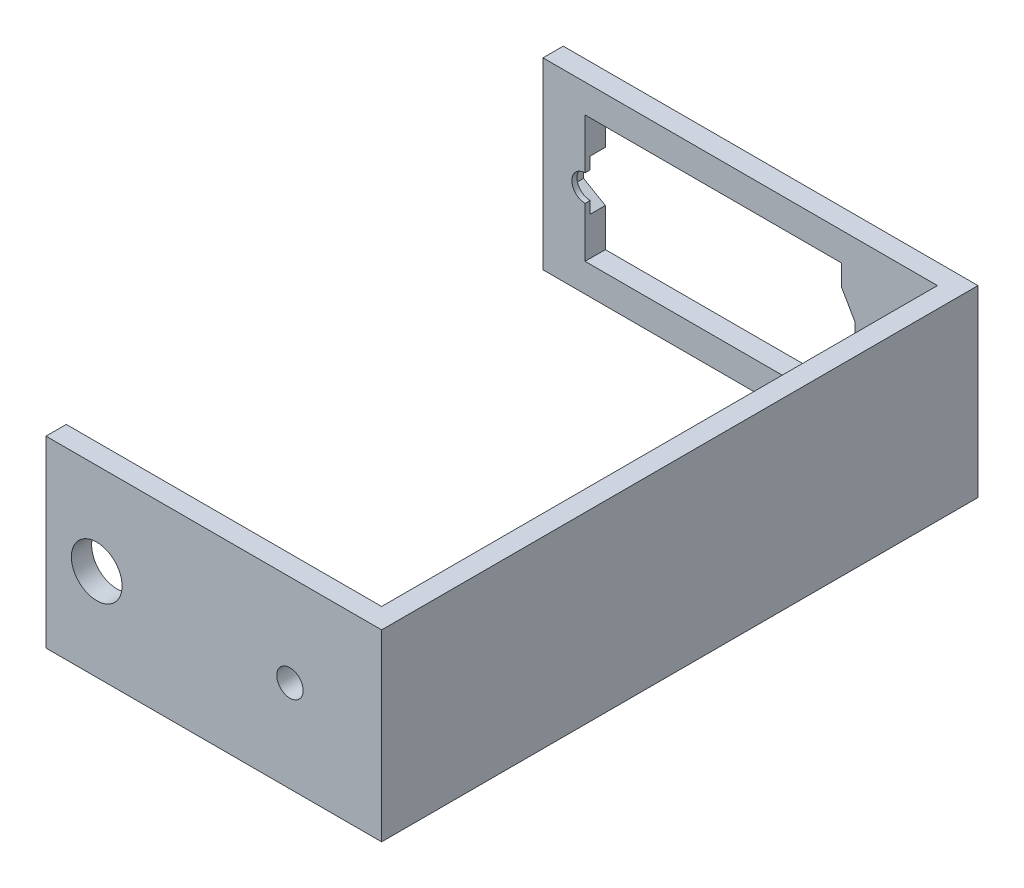
SolidWorks part; units mm, degrees
ref_plane "Front Plane" through (0, 0, 0) normal (0, 0, 1) x (1, 0, 0)
ref_plane "Top Plane" through (0, 0, 0) normal (0, 1, 0) x (1, 0, 0)
ref_plane "Right Plane" through (0, 0, 0) normal (1, 0, 0) x (0, 0, -1)
sketch "Sketch2" plane through (-4.7256, 0, 0) normal (1, 0, 0) x (0, 1, 0)
  line L0 (-22.4995, 27.5679) -> (-27.1995, 27.5679) construction
  line L1 (-33.8995, 25.5679) -> (-15.7995, 25.5679)
  line L2 (-33.8995, 25.5679) -> (-33.8995, -29.2321)
  line L3 (-33.8995, -29.2321) -> (-15.7995, -29.2321)
  line L4 (-15.7995, 25.5679) -> (-15.7995, -29.2321)
  line L5 (-22.4995, 27.5679) -> (-27.1995, 27.5679) construction
  line L6 (-24.8495, 27.5679) -> (-24.8495, 25.5679) construction
  line L7 (-30.8995, -25.9321) -> (-30.8995, -28.9321) construction
  dimension "D1" = 2
  dimension "D2" = 0.3
  dimension "D3" = 3
extrude "Boss-Extrude1" add sketch "Sketch2" along normal blind 2 from offset 26.09
sketch "Sketch3" plane through (0, 0, 25.5679) normal (0, 0, 1) x (1, 0, 0)
  line L0 (23.3644, -15.7995) -> (21.3644, -15.7995) construction
  line L1 (23.3644, -33.8995) -> (-9.7256, -33.8995)
  line L2 (23.3644, -33.8995) -> (23.3644, -15.7995)
  line L3 (23.3644, -15.7995) -> (-9.7256, -15.7995)
  line L4 (-9.7256, -33.8995) -> (-9.7256, -15.7995)
  line L5 (23.3644, -15.7995) -> (23.3644, -33.8995) construction
  circle A0 centre (-4.7256, -24.8495) radius 2.35 construction
  circle A1 centre (-4.7256, -24.8495) radius 2.35 construction
  circle A2 centre (-4.7256, -24.8495) radius 2.5
  dimension "D1" = 5
  dimension "D2" = 5
extrude "Boss-Extrude2" add sketch "Sketch3" along normal blind 2
sketch "Sketch4" plane through (0, 0, -29.2321) normal (0, 0, -1) x (-1, 0, 0)
  line L0 (-23.3644, -33.8995) -> (-21.3644, -33.8995) construction
  line L1 (-23.3644, -15.7995) -> (17.5256, -15.7995)
  line L2 (-23.3644, -15.7995) -> (-23.3644, -33.8995)
  line L3 (-23.3644, -33.8995) -> (17.5256, -33.8995)
  line L4 (17.5256, -15.7995) -> (17.5256, -33.8995)
  line L5 (13.3756, -22.3669) -> (13.3756, -15.7995)
  line L6 (11.2256, -23.6082) -> (11.2256, -26.0908)
  line L7 (11.2256, -26.0908) -> (13.3756, -27.3321)
  line L8 (13.3756, -27.3321) -> (15.5256, -26.0908)
  line L9 (15.5256, -26.0908) -> (15.5256, -23.6082)
  line L10 (15.5256, -23.6082) -> (13.3756, -22.3669)
  line L11 (13.3756, -22.3669) -> (11.2256, -23.6082)
  line L12 (13.3756, -27.3321) -> (13.3756, -33.8995)
  line L13 (-0.4744, -30.8995) -> (-0.4744, -18.7995) construction
  line L14 (-12.1744, -26.0908) -> (-14.3244, -27.3321)
  line L15 (-13.2494, -22.9875) -> (-13.2494, -26.7114)
  line L16 (13.3756, -22.3669) -> (13.3756, -27.3321)
  line L19 (-11.7244, -18.7995) -> (-11.7244, -30.8995)
  line L20 (-11.7244, -30.8995) -> (10.7756, -30.8995)
  line L21 (10.7756, -30.8995) -> (10.7756, -18.7995)
  line L22 (10.7756, -18.7995) -> (-11.7244, -18.7995)
  line L23 (-11.7244, -18.7995) -> (-11.7244, -30.8995) construction
  line L24 (-11.7244, -30.8995) -> (10.7756, -30.8995) construction
  line L25 (10.7756, -30.8995) -> (10.7756, -18.7995) construction
  line L26 (10.7756, -18.7995) -> (-11.7244, -18.7995) construction
  line L27 (-14.3244, -27.3321) -> (-16.4744, -26.0908)
  line L28 (-16.4744, -26.0908) -> (-16.4744, -23.6082)
  line L29 (-16.4744, -23.6082) -> (-14.3244, -22.3669)
  line L30 (-14.3244, -22.3669) -> (-12.1744, -23.6082)
  line L31 (-11.9244, -18.5995) -> (-11.9244, -31.0995)
  line L32 (-11.9244, -31.0995) -> (10.9756, -31.0995)
  line L33 (10.9756, -31.0995) -> (10.9756, -18.5995)
  line L34 (10.9756, -18.5995) -> (-11.9244, -18.5995)
  line L35 (-11.9244, -18.5995) -> (-11.9244, -20.6926)
  line L36 (-11.9244, -31.0995) -> (13.3756, -31.0995)
  line L38 (13.3756, -18.5995) -> (-11.9244, -18.5995)
  line L39 (-12.1744, -23.6082) -> (-12.1744, -26.0908)
  line L40 (-13.2494, -22.9875) -> (-11.9244, -20.6926)
  line L41 (-13.2494, -26.7114) -> (-11.9244, -29.0064)
  line L42 (-11.9244, -29.0064) -> (-11.9244, -31.0995)
  line L43 (-11.9244, -20.6926) -> (-11.9244, -29.0064) construction
  circle A0 centre (-14.3244, -24.8495) radius 1.1 construction
  circle A1 centre (13.3756, -24.8495) radius 1.1 construction
  circle A2 centre (-14.3244, -24.8495) radius 1.1 construction
  circle A3 centre (13.3756, -24.8495) radius 1.1 construction
  circle A4 centre (13.3756, -24.8495) radius 2.15 construction
  circle A5 centre (-14.3244, -24.8495) radius 2.15 construction
  line M26 (-21.3644, -33.8995) -> (-21.3644, -15.7995)
  line M27 (-21.3644, -15.7995) -> (-23.3644, -15.7995)
  line M28 (-23.3644, -15.7995) -> (-23.3644, -33.8995)
  line M29 (-23.3644, -33.8995) -> (-21.3644, -33.8995)
  dimension "D1" = 4.3
  dimension "D4" = 2
  dimension "D2" = 0
  dimension "D3" = 0.2
extrude "Boss-Extrude3" add sketch "Sketch4" along normal blind 2 contours M29 M26 M27 M28 | L38 L5 L1 L3 L12 L36 L35 L30 L39 L14 L27 L28 L29 M26 | L8 L12 L3 L4 L1 L5 L10 L9 | L30 L29 L28 L27 L14 L15 | L10 L16 L8 L9 region at (22.3644, -24.8495, -29.2321) region at (3.9944, -16.1912, -29.2321) region at (-15.5842, -24.8495, -29.2321) region at (-14.3312, -24.8495, -29.2321) region at (14.7393, -24.8495, -29.2321)
extrude "Cut-Extrude5" cut sketch "Sketch4<3>" against normal blind 1.5 from surface contours L30 L29 L28 L27 L14 L15 | L10 L16 L8 L9 region at (-14.3312, -24.8495, -29.2321) region at (14.7393, -24.8495, -29.2321) starting at face at (5.9306, -24.8495, -31.2321)
sketch "Sketch4<3>" plane through (0, 0, -29.2321) normal (0, 0, -1) x (-1, 0, 0) same geometry as "Sketch4"
sketch "Sketch5" plane through (0, 0, -31.2321) normal (0, 0, -1) x (-1, 0, 0)
  line L0 (13.3756, -27.3321) -> (13.3756, -22.3669) construction
  point P0 (-14.3244, -24.8495)
  point P3 (13.3756, -24.8495)
hole_wizard "M2 Clearance Hole1" positions "Sketch5" profile "Sketch6" hole size "M2" standard "ANSI Metric" end condition through all
sketch "Sketch6" plane through (14.3244, -24.8495, -31.2321) normal (1, 0, 0) x (0, 1, 0)
  line L0 (0, 0) -> (0, 58.8)
  line L1 (0, 58.8) -> (1.3, 58.8)
  line L2 (1.3, 58.8) -> (1.3, 0)
  line L5 (1.3, 0) -> (0, 0)
  line L11 (0, -6.35) -> (0, 107.95) construction
  dimension "Thru Hole Dia." = 2.6
  dimension "Thru Hole Depth" = 58.8
